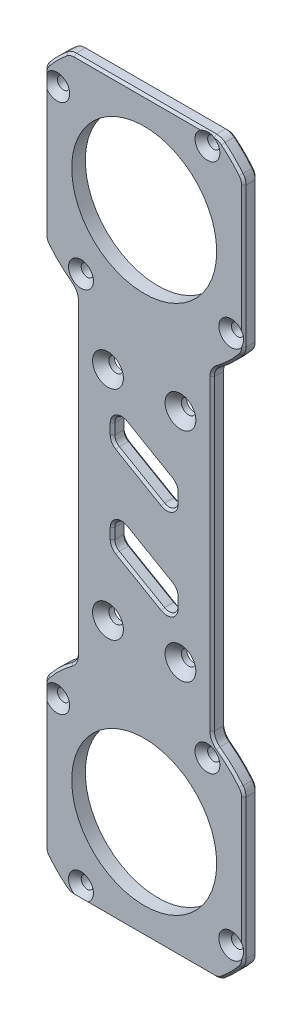
SolidWorks part; units mm, degrees
material "6061 合金"
ref_plane "前视基准面" through (0, 0, 0) normal (0, 0, 1) x (1, 0, 0)
ref_plane "上视基准面" through (0, 0, 0) normal (0, 1, 0) x (1, 0, 0)
ref_plane "右视基准面" through (0, 0, 0) normal (1, 0, 0) x (0, 0, -1)
other "Configuration Table"
sketch "草图1" plane through (0, 0, 0) normal (0, 0, 1) x (1, 0, 0)
  line L0 (0, 0) -> (115.9732, 0) construction
  line L5 (0, 0) -> (0, 105.0568) construction
  line L18 (-22, 80.5) -> (22, 80.5)
  line L19 (22, 80.5) -> (22, 36.5)
  line L20 (22, 36.5) -> (15, 36.5)
  line L21 (15, 36.5) -> (15, -36.5)
  line L22 (-15, 36.5) -> (-15, -36.5)
  line L23 (-22, 36.5) -> (-15, 36.5)
  line L24 (-22, 80.5) -> (-22, 36.5)
  line L25 (22, -36.5) -> (15, -36.5)
  line L26 (22, -80.5) -> (22, -36.5)
  line L27 (-22, -36.5) -> (-15, -36.5)
  line L28 (-22, -80.5) -> (-22, -36.5)
  line L29 (-22, -80.5) -> (22, -80.5)
  circle A4 centre (0, 58.5) radius 27.5
  circle A5 centre (0, 58.5) radius 15.25
  circle A6 centre (0, -58.5) radius 15.25
  circle A7 centre (0, -58.5) radius 27.5
  point P8 (22, 58.5)
  point P17 (0, 80.5)
  point P20 (15, 0)
  point P21 (-15, 0)
  dimension "D5" = 30
  dimension "D6" = 117
  dimension "D1" = 30.5
  dimension "D3" = 55
  dimension "D2" = 44
  dimension "D4" = 44
extrude "凸台-拉伸1" add sketch "草图1" along normal blind 3 contours L22 A7 L21 A4 | L21 A4 L20 | L23 A4 L22 | A7 L27 L22 | A7 L21 L25 | A7 L26 L25 L21 L22 L27 L28 L29 A6 | L19 A4 L18 L24 L23 L22 L21 L20 A5
fillet "圆角1" radius 3 16 edges at (-22, 42, 1.5) (-22, 75, 1.5) (-15, 35.4511, 1.5) (15, 35.4511, 1.5) (22, 75, 1.5) (22, 42, 1.5) (-16.5, 80.5, 1.5) (16.5, 80.5, 1.5) (15, -35.4511, 1.5) (22, -42, 1.5) (22, -75, 1.5) (16.5, -80.5, 1.5) (-16.5, -80.5, 1.5) (-22, -75, 1.5) (-22, -42, 1.5) (-15, -35.4511, 1.5)
sketch "草图3" plane through (0, 0, 3) normal (0, 0, 1) x (1, 0, 0)
  line L0 (0, 0) -> (0, -58.5) construction
  line L1 (0, -58.5) -> (23.75, -58.5) construction
  line L2 (0, -58.5) -> (16.7938, -41.7062) construction
  line L3 (19.2142, -44.5401) -> (0, -58.5) construction
  line L4 (0, 0) -> (-15, 0) construction
  line L5 (-15, 33.8779) -> (-15, -33.8779) construction
  circle A0 centre (0, -58.5) radius 23.75 construction
  circle A2 centre (13.9599, -39.2858) radius 1.5
  circle A3 centre (19.2142, -72.4599) radius 1.5
  circle A5 centre (-13.9599, -77.7142) radius 1.5
  circle A7 centre (-19.2142, -44.5401) radius 1.5
  circle A10 centre (19.2142, 44.5401) radius 1.5
  circle A12 centre (13.9599, 77.7142) radius 1.5
  circle A14 centre (-19.2142, 72.4599) radius 1.5
  circle A16 centre (-13.9599, -39.2858) radius 1.5 construction
  circle A17 centre (-13.9599, 39.2858) radius 1.5
  point P9 (13.9599, -39.2858)
  point P16 (19.2142, -72.4599)
  point P20 (-13.9599, -77.7142)
  point P24 (-19.2142, -44.5401)
  point P30 (19.2142, 44.5401)
  point P34 (13.9599, 77.7142)
  point P38 (-19.2142, 72.4599)
  point P89 (-13.9599, 39.2858)
  dimension "D1" = 47.5
  dimension "D2" = 45
  dimension "D3" = 36
  dimension "D5" = 4
hole_wizard "M2.5 十字槽半沉头木螺钉的锥形沉头孔1" positions "草图3" profile "草图4" countersink size "M2.5" standard "GB"
sketch "草图4" plane through (-13.9599, 39.2858, 3) normal (1, 0, 0) x (0, -1, 0)
  line L0 (0, 0) -> (0, 3.8112)
  line L1 (0, 3.8112) -> (1.35, 3)
  line L2 (1.35, 3) -> (1.35, 1.4)
  line L3 (1.35, 1.4) -> (2.75, 0)
  line L5 (2.75, 0) -> (0, 0)
  line L6 (-1.35, 1.4) -> (-2.75, 0) construction
  line L10 (0, 3.8112) -> (-1.35, 3) construction
  line L11 (0, -6.35) -> (0, 107.95) construction
  dimension "孔直径" = 2.7
  dimension "孔深度" = 3
  dimension "近端锥形沉头孔直径" = 5.5
  dimension "近端锥形沉头孔角度" = 90
  dimension "导头角度" = 118
sketch "草图5" plane through (0, 0, 3) normal (0, 0, 1) x (1, 0, 0)
  line L0 (0, 0) -> (0, -27.8562) construction
  line L1 (0, 0) -> (15, 0) construction
  line L2 (15, 33.8779) -> (15, -33.8779) construction
  line L11 (-15, 33.8779) -> (-15, -33.8779) construction
  line L20 (7, 9.4226) -> (-7, 17.5056)
  line L21 (-7, 17.5056) -> (-7, 10.5774)
  line L22 (-7, 10.5774) -> (7, 2.4944)
  line L23 (7, 2.4944) -> (7, 9.4226)
  line L26 (-7, -2.4944) -> (-7, -9.4226)
  line L27 (-7, -9.4226) -> (7, -17.5056)
  line L28 (7, -17.5056) -> (7, -10.5774)
  line L29 (7, -10.5774) -> (-7, -2.4944)
  line L32 (-7, 17.5056) -> (7, 2.4944) construction
  line L33 (-7, 10.5774) -> (7, 9.4226) construction
  line L34 (7, 29.4226) -> (-7, 37.5056)
  line L35 (-7, 37.5056) -> (-7, 30.5774)
  line L36 (-7, 30.5774) -> (7, 22.4944)
  line L37 (7, 22.4944) -> (7, 29.4226)
  line L38 (-7, -9.4226) -> (7, -10.5774) construction
  line L39 (-7, -2.4944) -> (7, -17.5056) construction
  line L40 (0, 10) -> (0, -10) construction
  point P13 (0, 0)
  dimension "D2" = 3
  dimension "D3" = 20
  dimension "D4" = 0
  dimension "D8" = 8
  dimension "D9" = 8
  dimension "D10" = 6
  dimension "D5" = 60
extrude "切除-拉伸1" cut sketch "草图5" against normal blind 10
fillet "圆角2" radius 2 8 edges at (7, -10.5774, 1.5) (7, -17.5056, 1.5) (-7, -9.4226, 1.5) (-7, -2.4944, 1.5) (-7, 10.5774, 1.5) (7, 2.4944, 1.5) (7, 9.4226, 1.5) (-7, 17.5056, 1.5)
sketch "草图6" plane through (0, 0, 3) normal (0, 0, 1) x (1, 0, 0)
  line L0 (0, 0) -> (15, 0) construction
  line L1 (15, 33.8779) -> (15, -33.8779) construction
  line L2 (0, 0) -> (0, 43.25) construction
  circle A0 centre (0, 58.5) radius 15.25 construction
  circle A1 centre (8, 24) radius 1.5
  circle A2 centre (-8, 24) radius 1.5
  circle A3 centre (8, -24) radius 1.5
  circle A4 centre (-8, -24) radius 1.5
  point P5 (8, 24)
  point P11 (-8, 24)
  point P13 (8, -24)
  point P15 (-8, -24)
  dimension "D1" = 3
  dimension "D2" = 7
  dimension "D3" = 24
hole_wizard "M3 十字槽半沉头木螺钉的锥形沉头孔2" positions "草图6" profile "草图7" countersink size "M3" standard "GB"
sketch "草图7" plane through (-8, -24, 3) normal (1, 0, 0) x (0, -1, 0)
  line L0 (0, 0) -> (0, 3.9614)
  line L1 (0, 3.9614) -> (1.6, 3)
  line L2 (1.6, 3) -> (1.6, 1.8)
  line L3 (1.6, 1.8) -> (3.4, 0)
  line L5 (3.4, 0) -> (0, 0)
  line L6 (-1.6, 1.8) -> (-3.4, 0) construction
  line L10 (0, 3.9614) -> (-1.6, 3) construction
  line L11 (0, -6.35) -> (0, 107.95) construction
  dimension "孔直径" = 3.2
  dimension "孔深度" = 3
  dimension "近端锥形沉头孔直径" = 6.8
  dimension "近端锥形沉头孔角度" = 90
  dimension "导头角度" = 118
sketch "草图8" plane through (0, 0, 3) normal (0, 0, 1) x (1, 0, 0)
  circle A0 centre (0, 58.5) radius 16
  circle A1 centre (0, -58.5) radius 16
  dimension "D1" = 32
  dimension "D2" = 32
extrude "切除-拉伸2" cut sketch "草图8" against normal blind 10
chamfer "倒角1" distance 0.5 angle 45 64 edges at (0, -80.5, 0) (0, -80.5, 3) (-16.4728, -80.3266, 3) (-16.4728, -80.3266, 0) (16.4728, -80.3266, 3) (16.4728, -80.3266, 0) (-19.4454, -77.9454, 3) (-19.4454, -77.9454, 0) (19.4454, -77.9454, 3) (19.4454, -77.9454, 0) (-21.8266, -74.9728, 3) (-21.8266, -74.9728, 0) (21.8266, -74.9728, 3) (21.8266, -74.9728, 0) (-22, -58.5, 0) (-22, -58.5, 3) (22, -58.5, 0) (22, -58.5, 3) (-21.8266, -42.0272, 3) (-21.8266, -42.0272, 0) (21.8266, -42.0272, 3) (21.8266, -42.0272, 0) (-18.9332, -38.5555, 3) (-18.9332, -38.5555, 0) (18.9332, -38.5555, 3) (18.9332, -38.5555, 0) (-15.325, -35.2359, 3) (-15.325, -35.2359, 0) (15.325, -35.2359, 3) (15.325, -35.2359, 0) (-15, 0, 0) (-15, 0, 3) (15, 0, 3) (15, 0, 0) (-15.325, 35.2359, 3) (-15.325, 35.2359, 0) (15.325, 35.2359, 3) (15.325, 35.2359, 0) (-18.9332, 38.5555, 3) (-18.9332, 38.5555, 0) (18.9332, 38.5555, 3) (18.9332, 38.5555, 0) (-21.8266, 42.0272, 3) (-21.8266, 42.0272, 0) (21.8266, 42.0272, 3) (21.8266, 42.0272, 0) (-22, 58.5, 0) (-22, 58.5, 3) (22, 58.5, 3) (22, 58.5, 0) (-21.8266, 74.9728, 3) (-21.8266, 74.9728, 0) (21.8266, 74.9728, 3) (21.8266, 74.9728, 0) (-19.4454, 77.9454, 3) (-19.4454, 77.9454, 0) (19.4454, 77.9454, 3) (19.4454, 77.9454, 0) (-16.4728, 80.3266, 3) (-16.4728, 80.3266, 0) (16.4728, 80.3266, 3) (16.4728, 80.3266, 0) (0, 80.5, 3) (0, 80.5, 0)
chamfer "倒角2" distance 0.5 angle 45 32 edges at (-1, -12.8868, 3) (-1, -12.8868, 0) (6, -15.7735, 0) (6, -15.7735, 3) (-6.7321, -9.2679, 0) (-6.7321, -9.2679, 3) (7, -12.8868, 3) (7, -12.8868, 0) (-7, -7.1132, 3) (-7, -7.1132, 0) (6.7321, -10.7321, 0) (6.7321, -10.7321, 3) (-6, -4.2265, 0) (-6, -4.2265, 3) (1, -7.1132, 0) (1, -7.1132, 3) (-1, 7.1132, 0) (-1, 7.1132, 3) (6, 4.2265, 0) (6, 4.2265, 3) (-6.7321, 10.7321, 0) (-6.7321, 10.7321, 3) (7, 7.1132, 0) (7, 7.1132, 3) (-7, 12.8868, 3) (-7, 12.8868, 0) (6.7321, 9.2679, 0) (6.7321, 9.2679, 3) (-6, 15.7735, 0) (-6, 15.7735, 3) (1, 12.8868, 0) (1, 12.8868, 3)
